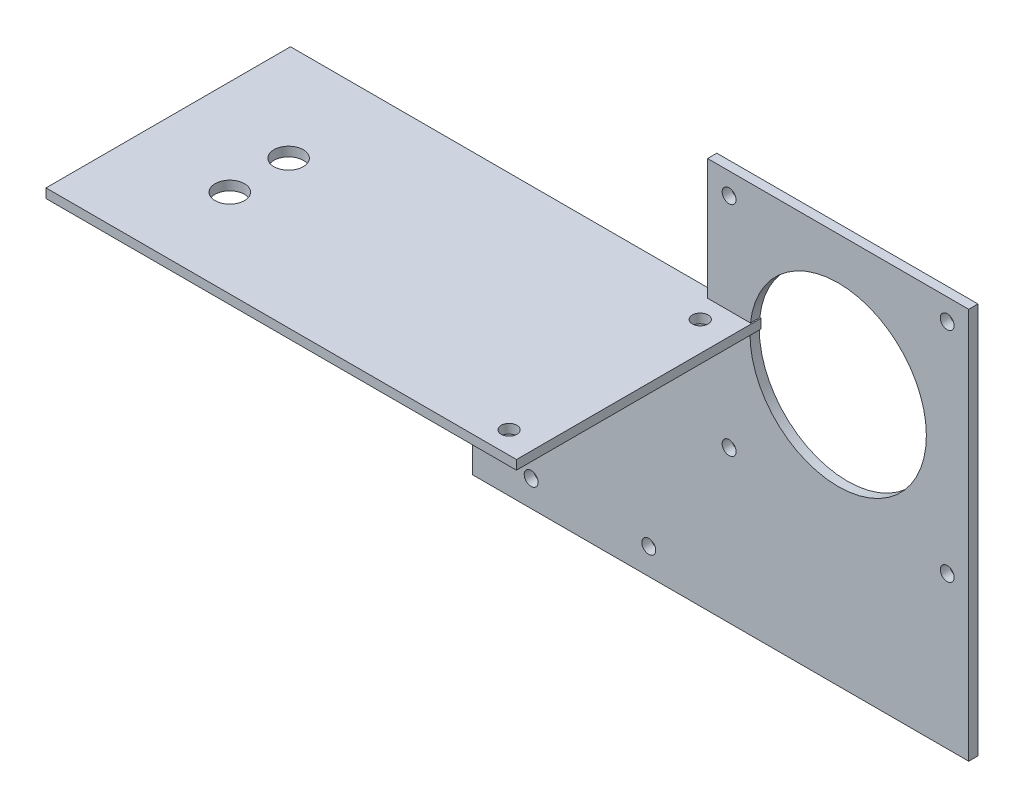
SolidWorks part; units mm, degrees
ref_plane "Front Plane" through (0, 0, 0) normal (0, 0, 1) x (1, 0, 0)
ref_plane "Top Plane" through (0, 0, 0) normal (0, 1, 0) x (1, 0, 0)
ref_plane "Right Plane" through (0, 0, 0) normal (1, 0, 0) x (0, 0, -1)
sketch "Sketch1" plane through (0, 0, 0) normal (0, 0, 1) x (1, 0, 0)
  line L0 (12.7, 52.75) -> (38.1, 52.75) construction
  line L1 (12.7, 5.65) -> (38.1, 5.65) construction
  line L2 (0, 58.4) -> (0, 0)
  line L3 (0, 0) -> (107.2, 0)
  line L4 (55.45, 79.882) -> (102.55, 79.882) construction
  line L5 (102.55, 79.882) -> (102.55, 32.782) construction
  line L6 (12.7, 52.75) -> (12.7, 5.65) construction
  line L7 (55.45, 32.782) -> (55.45, 79.882) construction
  line L8 (55.45, 32.782) -> (102.55, 32.782) construction
  line L9 (38.1, 52.75) -> (38.1, 5.65) construction
  line L10 (55.45, 79.882) -> (102.55, 32.782) construction
  line L11 (102.55, 79.882) -> (55.45, 32.782) construction
  line L12 (0, 58.4) -> (50.8, 58.4)
  line L13 (50.8, 58.4) -> (50.8, 84.532)
  line L14 (50.8, 84.532) -> (107.2, 84.532)
  line L15 (107.2, 84.532) -> (107.2, 0)
  circle A0 centre (102.55, 79.882) radius 1.5
  circle A1 centre (102.55, 32.782) radius 1.5
  circle A2 centre (55.45, 32.782) radius 1.5
  circle A3 centre (55.45, 79.882) radius 1.5
  circle A4 centre (12.7, 52.75) radius 1.5
  circle A5 centre (38.1, 52.75) radius 1.5
  circle A6 centre (12.7, 5.65) radius 1.5
  circle A7 centre (38.1, 5.65) radius 1.5
  circle A8 centre (79, 56.332) radius 19.05
  point P3 (12.7, 29.2)
  point P21 (0, 29.2)
  dimension "D3" = 3
  dimension "D10" = 38.1
  dimension "D1" = 58.4
  dimension "D2" = 107.2
  dimension "D4" = 47.1
  dimension "D5" = 47.1
  dimension "D6" = 2.068
  dimension "D7" = 25.4
  dimension "D8" = 47.1
  dimension "D9" = 12.7
  dimension "D11" = 4.65
  dimension "D12" = 4.65
  dimension "D13" = 4.65
extrude "Boss-Extrude1" add sketch "Sketch1" against normal blind 2
sketch "Sketch2" plane through (0, 0, -2) normal (0, 0, -1) x (-1, 0, 0)
  line L0 (0, 58.4) -> (41.275, 58.4)
  line L1 (0, 58.4) -> (0, 0) construction
  line L2 (0, 56.4) -> (-60.325, 56.4)
  line L3 (-60.325, 56.4) -> (-60.325, 58.4)
  line L5 (-60.325, 58.4) -> (0, 58.4)
  line L6 (41.275, 58.4) -> (41.275, 56.4)
  line L7 (41.275, 56.4) -> (0, 56.4)
  point P8 (0, 0)
  point P9 (2.7049, 63.0959)
  point P11 (0, 0)
  dimension "D1" = 60.325
  dimension "D2" = 2
  dimension "D3" = 41.275
extrude "Boss-Extrude2" add sketch "Sketch2" against normal blind 52.8
sketch "Sketch3" plane through (0, 58.4, 0) normal (0, 1, 0) x (1, 0, 0)
  line L0 (53.975, -4.7625) -> (53.975, -46.0375) construction
  line L2 (60.325, -50.8) -> (60.325, 2) construction
  line L3 (-41.275, -50.8) -> (60.325, -50.8) construction
  circle A0 centre (53.975, -4.7625) radius 1.7
  circle A1 centre (53.975, -46.0375) radius 1.7
  dimension "D1" = 3.4
  dimension "D2" = 41.275
  dimension "D3" = 4.7625
  dimension "D4" = 6.35
extrude "Cut-Extrude1" cut sketch "Sketch3" against normal through all
sketch "Sketch4" plane through (0, 58.4, 0) normal (0, 1, 0) x (1, 0, 0)
  line L0 (-20.6375, 2) -> (-20.6375, -50.8) construction
  line L2 (-41.275, -50.8) -> (60.325, -50.8) construction
  line L3 (-41.275, -50.8) -> (-41.275, 2) construction
  line L4 (50.8, 2) -> (-41.275, 2) construction
  circle A0 centre (-20.6375, -19.05) radius 3.175
  circle A1 centre (-20.6375, -31.75) radius 3.175
  point P12 (0, 0)
  dimension "D2" = 6.35
  dimension "D3" = 6.35
  dimension "D1" = 20.6375
  dimension "D4" = 12.7
  dimension "D5" = 19.05
extrude "Cut-Extrude2" cut sketch "Sketch4" against normal blind 10
